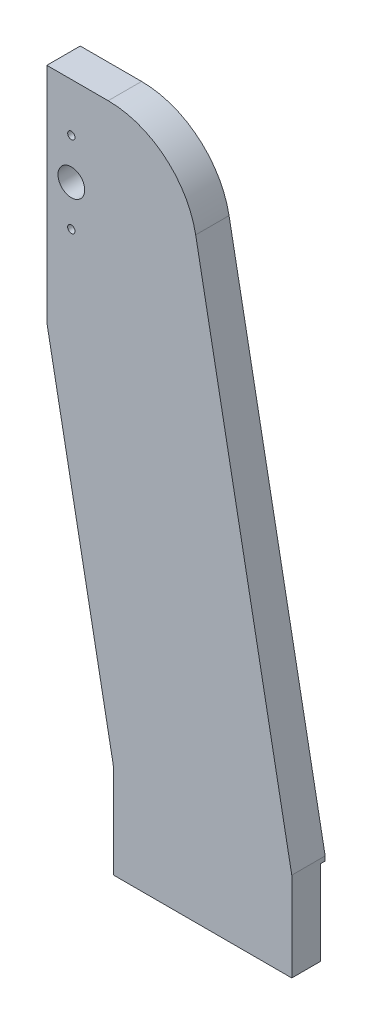
SolidWorks part; units mm, degrees
material "3.3547 (EN-AW 5083)"
ref_plane "Alzado" through (0, 0, 0) normal (0, 0, 1) x (1, 0, 0)
ref_plane "Planta" through (0, 0, 0) normal (0, 1, 0) x (1, 0, 0)
ref_plane "Vista lateral" through (0, 0, 0) normal (1, 0, 0) x (0, 0, -1)
sketch "Croquis1" plane through (0, 0, 0) normal (0, 0, 1) x (1, 0, 0)
  line L0 (80, 0) -> (80, 40)
  line L1 (-30, 300) -> (-2.4542, 300)
  line L2 (-30, 300) -> (-30, 200)
  line L3 (0, 0) -> (80, 0)
  line L4 (36.8447, 267.4562) -> (80, 40)
  line L9 (-30, 200) -> (-0.3505, 43.7281)
  line L11 (0, 40) -> (0, 0)
  arc A2 (36.8447, 267.4562) -> (-2.4542, 300) centre (-2.4542, 260) ccw
  arc A3 (0, 40) -> (-0.3505, 43.7281) centre (-20, 40) ccw
  point P14 (0, 41.8805)
  dimension "D7" = 20
  dimension "D9" = 40
  dimension "D1" = 40
  dimension "D2" = 300
  dimension "D3" = 80
  dimension "D4" = 30
  dimension "D5" = 100
  dimension "D6" = 40
extrude "Saliente-Extruir1" add sketch "Croquis1" along normal blind 15
sketch "Croquis2" plane through (0, 0, 0) normal (0, 0, -1) x (-1, 0, 0)
  line L0 (2.4542, 300) -> (30, 300) construction
  line L2 (30, 300) -> (30, 200) construction
  circle A0 centre (19, 260) radius 6
  dimension "D3" = 12
  dimension "D1" = 40
  dimension "D2" = 11
extrude "Cortar-Extruir1" cut sketch "Croquis2" against normal through all
hole_wizard "Perforador para roscar para macho de roscar para M44" positions "Croquis7" profile "Croquis8" hole size "M4" standard "DIN"
sketch "Croquis7" plane through (0, 0, 15) normal (0, 0, 1) x (1, 0, 0)
  line L0 (-19, 278.25) -> (-19, 241.75)
  circle A0 centre (-19, 260) radius 6 construction
  point P1 (-19, 278.25)
  point P2 (-19, 241.75)
  dimension "D1" = 18.25
  dimension "D2" = 18.25
sketch "Croquis8" plane through (-19, 278.25, 15) normal (1, 0, 0) x (0, -1, 0)
  line L0 (0, 0) -> (0, 7.9914)
  line L1 (0, 7.9914) -> (1.65, 7)
  line L2 (1.65, 7) -> (1.65, 0)
  line L5 (1.65, 0) -> (0, 0)
  line L10 (0, 7.9914) -> (-1.65, 7) construction
  line L11 (0, -6.35) -> (0, 107.95) construction
  dimension "Diámetro de taladro" = 3.3
  dimension "Profundidad de taladro" = 7
  dimension "Ángulo de perforador" = 118
sketch "Croquis9" plane through (0, 0, 0) normal (0, 0, -1) x (-1, 0, 0)
  line L1 (0, 0) -> (-80, 0)
  line L2 (0, 0) -> (0, 38)
  line L3 (0, 38) -> (-80, 38)
  line L4 (-80, 0) -> (-80, 38)
  dimension "D1" = 80
  dimension "D2" = 38
extrude "Cortar-Extruir2" cut sketch "Croquis9" against normal blind 2
hole_wizard "Perforador para roscar para macho de roscar para M45" positions "Croquis10" profile "Croquis11" hole size "M4" standard "DIN"
sketch "Croquis10" plane through (-30, 0, 0) normal (-1, 0, 0) x (0, 0, 1)
  line L0 (15, 300) -> (0, 300) construction
  line L1 (15, 300) -> (15, 200) construction
  point P0 (9, 285)
  point P2 (9, 235)
  dimension "D1" = 15
  dimension "D2" = 65
  dimension "D3" = 6
  dimension "D4" = 6
sketch "Croquis11" plane through (-30, 285, 9) normal (0, 1, 0) x (0, 0, 1)
  line L0 (0, 0) -> (0, 15.9914)
  line L1 (0, 15.9914) -> (1.65, 15)
  line L2 (1.65, 15) -> (1.65, 0)
  line L5 (1.65, 0) -> (0, 0)
  line L10 (0, 15.9914) -> (-1.65, 15) construction
  line L11 (0, -6.35) -> (0, 107.95) construction
  dimension "Diámetro de taladro" = 3.3
  dimension "Profundidad de taladro" = 15
  dimension "Ángulo de perforador" = 118
hole_wizard "Taladros de espiga de Ø4.0mm1" positions "Croquis12" profile "Croquis13" hole size "Ø4.0" standard "DIN"
sketch "Croquis12" plane through (-30, 0, 0) normal (-1, 0, 0) x (0, 0, 1)
  line L0 (15, 300) -> (0, 300) construction
  line L1 (15, 300) -> (15, 200) construction
  point P0 (9, 274)
  point P2 (9, 246)
  dimension "D1" = 26
  dimension "D2" = 54
  dimension "D3" = 6
  dimension "D4" = 6
sketch "Croquis13" plane through (-30, 274, 9) normal (0, 1, 0) x (0, 0, 1)
  line L0 (0, 0) -> (0, 16.2017)
  line L1 (0, 16.2017) -> (2, 15)
  line L2 (2, 15) -> (2, 0)
  line L5 (2, 0) -> (0, 0)
  line L10 (0, 16.2017) -> (-2, 15) construction
  line L11 (0, -6.35) -> (0, 107.95) construction
  dimension "Diámetro de taladro" = 4
  dimension "Profundidad de taladro" = 15
  dimension "Ángulo de perforador" = 118
